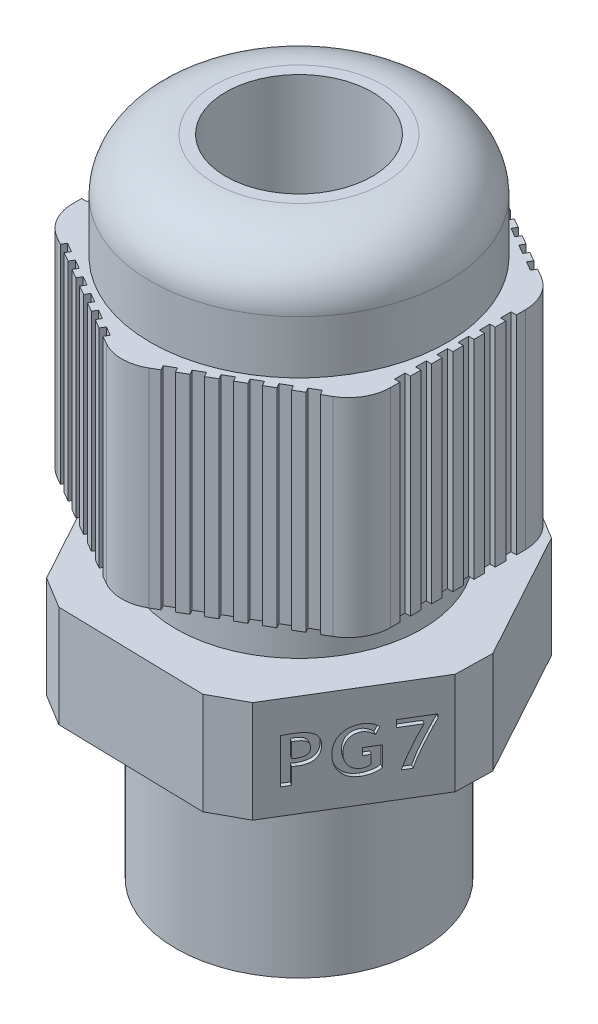
SolidWorks part; units mm, degrees
ref_plane "Front Plane" through (0, 0, 0) normal (0, 0, 1) x (1, 0, 0)
ref_plane "Top Plane" through (0, 0, 0) normal (0, 1, 0) x (1, 0, 0)
ref_plane "Right Plane" through (0, 0, 0) normal (1, 0, 0) x (0, 0, -1)
sketch "Sketch1" plane through (0, 0, 0) normal (0, 1, 0) x (1, 0, 0)
  circle A0 centre (0, 0) radius 5.8
  dimension "D1" = 11.6
extrude "Boss-Extrude1" add sketch "Sketch1" along normal blind 8.25
sketch "Sketch2" plane through (0, 8.25, 0) normal (0, 1, 0) x (1, 0, 0)
  line L1 (8.9465, -0.2087) -> (4.654, 7.6436)
  line L2 (4.654, 7.6436) -> (-4.2925, 7.8522)
  line L3 (-4.2925, 7.8522) -> (-8.9465, 0.2087)
  line L4 (-8.9465, 0.2087) -> (-4.654, -7.6436)
  line L5 (-4.654, -7.6436) -> (4.2925, -7.8522)
  line L6 (4.2925, -7.8522) -> (8.9465, -0.2087)
  circle A0 centre (0, 0) radius 7.75 construction
  dimension "D1" = 15.5
extrude "Boss-Extrude2" add sketch "Sketch2" along normal blind 4.8
sketch "Sketch3" plane through (0, 13.05, 0) normal (0, 1, 0) x (1, 0, 0)
  circle A0 centre (0, 0) radius 5.8
  dimension "D1" = 11.6
extrude "Boss-Extrude3" add sketch "Sketch3" along normal blind 2.5
sketch "Sketch4" plane through (0, 15.55, 0) normal (0, 1, 0) x (1, 0, 0)
  line L1 (7.5, 4.3301) -> (0, 8.6603)
  line L2 (0, 8.6603) -> (-7.5, 4.3301)
  line L3 (-7.5, 4.3301) -> (-7.5, -4.3301)
  line L4 (-7.5, -4.3301) -> (0, -8.6603)
  line L5 (0, -8.6603) -> (7.5, -4.3301)
  line L6 (7.5, -4.3301) -> (7.5, 4.3301)
  circle A0 centre (0, 0) radius 7.5 construction
  dimension "D1" = 15
  dimension "D2" = 0
extrude "Boss-Extrude4" add sketch "Sketch4" along normal blind 9.8
chamfer "Chamfer1" distance 1 distance2 1 6 edges at (-8.9465, 10.65, -0.2087) (-4.654, 10.65, 7.6436) (4.2925, 10.65, 7.8522) (8.9465, 10.65, 0.2087) (4.654, 10.65, -7.6436) (-4.2925, 10.65, -7.8522)
fillet "Fillet1" radius 2 6 edges at (7.5, 20.45, -4.3301) (7.5, 20.45, 4.3301) (0, 20.45, 8.6603) (-7.5, 20.45, 4.3301) (-7.5, 20.45, -4.3301) (0, 20.45, -8.6603)
sketch "Sketch5" plane through (0, 25.35, 0) normal (0, 1, 0) x (1, 0, 0)
  circle A0 centre (0, 0) radius 7
  dimension "D1" = 14
extrude "Boss-Extrude5" add sketch "Sketch5" along normal blind 5
fillet "Fillet2" radius 2.5 1 edges at (0, 30.35, 7) second distance 3 first distance on face at (0, 30.35, 7)
sketch "Sketch6" plane through (0, 30.35, 0) normal (0, 1, 0) x (1, 0, 0)
  circle A0 centre (0, 0) radius 3.45
  dimension "D1" = 6.9
extrude "Cut-Extrude1" cut sketch "Sketch6" against normal up to surface (30.35 mm away) up to face at (0, 0, 5.8)
sketch "Sketch7" plane through (-6.8002, 0, 3.7174) normal (-0.8774, 0, 0.4797) x (0.4797, 0, 0.8774)
  line L0 (-3.4745, 9.45) -> (3.4745, 9.45) construction
  line L1 (-3.4745, 13.05) -> (-3.4745, 8.25) construction
  line L2 (3.4745, 8.25) -> (3.4745, 13.05) construction
  line L3 (-3.4745, 8.25) -> (3.4745, 8.25) construction
  text T0 "<b>PG7</b>" font "Trebuchet MS" height in points 8
  dimension "D1" = 1.2
extrude "Cut-Extrude2" cut sketch "Sketch7" against normal blind 0.2
sketch "Sketch8" plane through (7.5, 0, 0) normal (1, 0, 0) x (0, 0, -1)
  line L0 (0, 25.35) -> (0, 15.55) construction
  line L1 (-3.1754, 25.35) -> (3.1754, 25.35) construction
  line L2 (-5.8, 15.55) -> (5.8, 15.55) construction
  line L3 (0.25, 25.35) -> (0.25, 15.55)
  line L4 (-0.25, 25.35) -> (-0.25, 15.55)
  line L5 (0.25, 25.35) -> (0.75, 25.35)
  line L6 (0.75, 25.35) -> (0.75, 15.55)
  line L7 (-3.1754, 15.55) -> (3.1754, 15.55) construction
  line L8 (0.75, 15.55) -> (0.25, 15.55)
  line L9 (1.75, 25.35) -> (1.75, 15.55)
  line L10 (1.25, 25.35) -> (1.25, 15.55)
  line L11 (1.25, 25.35) -> (1.75, 25.35)
  line L12 (1.75, 15.55) -> (1.25, 15.55)
  line L13 (2.75, 25.35) -> (2.75, 15.55)
  line L14 (2.25, 25.35) -> (2.25, 15.55)
  line L15 (2.25, 25.35) -> (2.75, 25.35)
  line L16 (2.75, 15.55) -> (2.25, 15.55)
  line L17 (-0.25, 25.35) -> (-0.75, 25.35)
  line L18 (-0.75, 25.35) -> (-0.75, 15.55)
  line L19 (-0.75, 15.55) -> (-0.25, 15.55)
  line L20 (-1.75, 25.35) -> (-1.75, 15.55)
  line L21 (-1.25, 25.35) -> (-1.75, 25.35)
  line L22 (-1.25, 25.35) -> (-1.25, 15.55)
  line L23 (-1.75, 15.55) -> (-1.25, 15.55)
  line L24 (-2.75, 25.35) -> (-2.75, 15.55)
  line L25 (-2.25, 25.35) -> (-2.75, 25.35)
  line L26 (-2.25, 25.35) -> (-2.25, 15.55)
  line L27 (-2.75, 15.55) -> (-2.25, 15.55)
  dimension "D1" = 2
  dimension "D3" = 0.25
  dimension "D4" = 0.25
  dimension "D5" = 0.5
  dimension "D7" = 0.5
  dimension "D8" = 0.5
  dimension "D10" = 0.5
  dimension "D2" = 2
  dimension "D6" = 3
  dimension "D9" = 3
extrude "Cut-Extrude3" cut sketch "Sketch8" against normal blind 0.25
sketch "Sketch9" plane through (0, 0, 0) normal (0, -1, 0) x (1, 0, 0)
  line L0 (-4.1962, 9) -> (-5.6962, 8.134)
  line L1 (9.8923, 0.866) -> (5.6962, 8.134)
  line L2 (4.1962, 9) -> (-4.1962, 9)
  line L3 (-5.6962, 8.134) -> (-9.8923, 0.866)
  line L4 (-9.8923, -0.866) -> (-5.6962, -8.134)
  line L5 (-4.1962, -9) -> (4.1962, -9)
  line L6 (5.6962, -8.134) -> (9.8923, -0.866)
  line L7 (-9.8923, 0.866) -> (-9.8923, -0.866)
  line L8 (5.6962, 8.134) -> (4.1962, 9)
  line L9 (9.8923, -0.866) -> (9.8923, 0.866)
  line L10 (4.1962, -9) -> (5.6962, -8.134)
  line L11 (-5.6962, -8.134) -> (-4.1962, -9)
  circle A0 centre (0, 0) radius 9 construction
  point P2 (10.3923, 0)
  point P3 (5.1962, 9)
  point P4 (-5.1962, 9)
  point P5 (-10.3923, 0)
  point P6 (-5.1962, -9)
  point P7 (5.1962, -9)
  dimension "D1" = 18
extrude "Boss-Extrude6" [suppressed] add sketch "Sketch9" against normal blind 5
pattern_circular "CirPattern1" count 6 over 360 about axis through (0, 25.35, 0) along (0, 1, 0) of "Cut-Extrude3" reverse direction yes
pattern_circular "CirPattern2" count 3 over 360 about axis through (0, 13.05, 0) along (0, 1, 0) of "Cut-Extrude2"
